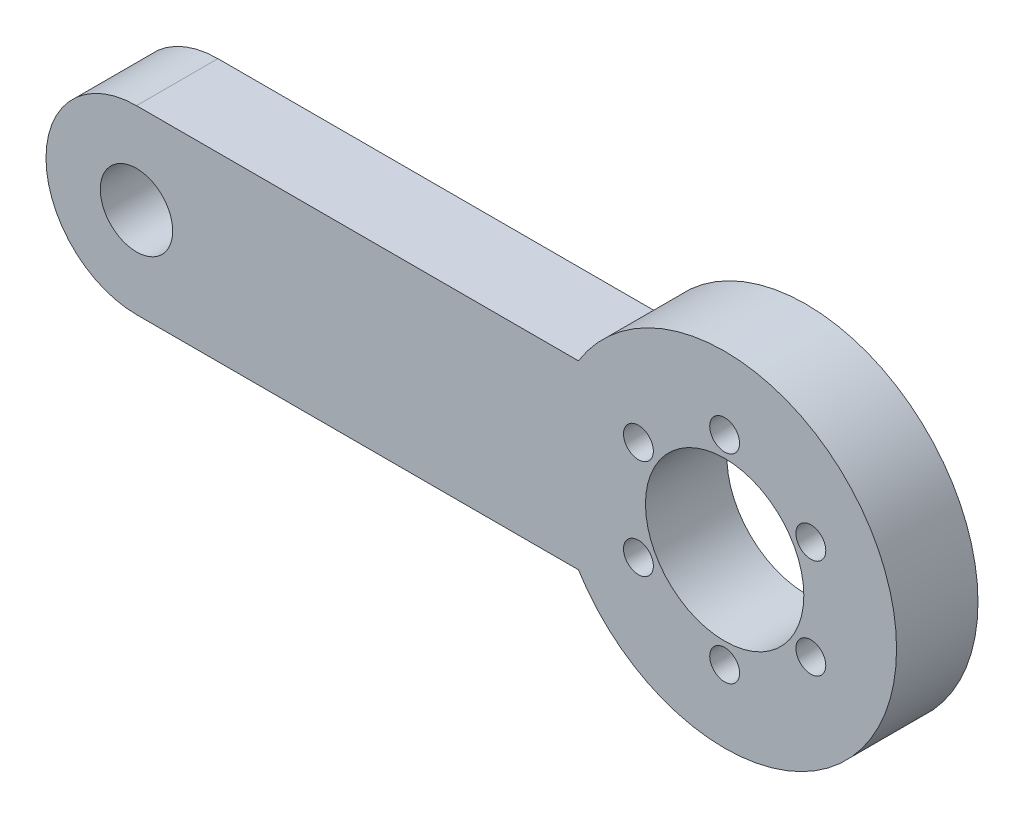
SolidWorks part; units mm, degrees
ref_plane "Plan de face" through (0, 0, 0) normal (0, 0, 1) x (1, 0, 0)
ref_plane "Plan de dessus" through (0, 0, 0) normal (0, 1, 0) x (1, 0, 0)
ref_plane "Plan de droite" through (0, 0, 0) normal (1, 0, 0) x (0, 0, -1)
sketch "Esquisse1" plane through (0, 0, 0) normal (0, 0, 1) x (1, 0, 0)
  line L1 (0, 0) -> (60, 0)
  line L2 (0, 0) -> (0, 20)
  line L3 (0, 20) -> (60, 20)
  line L4 (60, 0) -> (60, 20)
  dimension "D1" = 60
  dimension "D2" = 20
extrude "Boss.-Extru.1" add sketch "Esquisse1" along normal blind 9
sketch "Esquisse2" plane through (0, 0, 9) normal (0, 0, 1) x (1, 0, 0)
  line L0 (60, 25) -> (60, -5)
  line L1 (60, 0) -> (60, 20) construction
  line L2 (60, -5) -> (90, -5)
  line L3 (90, -5) -> (90, 25)
  line L4 (90, 10) -> (60, 10) construction
  line L5 (60, 25) -> (90, 25)
  dimension "D1" = 30
  dimension "D2" = 30
extrude "Boss.-Extru.2" add sketch "Esquisse2" against normal up to vertex (9 mm away) up to point (0, 20, 0)
sketch "Esquisse3" plane through (0, 0, 9) normal (0, 0, 1) x (1, 0, 0)
  line L0 (75, -5) -> (75, 25) construction
  line L1 (60, -5) -> (90, -5) construction
  line L2 (90, 25) -> (60, 25) construction
  circle A0 centre (75, 10) radius 8.75
  circle A1 centre (75, -1) radius 1.65
  circle A2 centre (65.4737, 4.5) radius 1.65
  circle A3 centre (65.4737, 15.5) radius 1.65
  circle A4 centre (75, 21) radius 1.65
  circle A5 centre (84.5263, 15.5) radius 1.65
  circle A6 centre (84.5263, 4.5) radius 1.65
  point P22 (75, 10)
  dimension "D1" = 17.5
  dimension "D2" = 11
  dimension "D3" = 3.3
  dimension "D4" = 6
extrude "Enlèv. mat.-Extru.1" cut sketch "Esquisse3" against normal through all both and the other way through all
sketch "Esquisse4" plane through (0, 0, 9) normal (0, 0, 1) x (1, 0, 0)
  line L0 (10, 20) -> (10, 0) construction
  line L1 (60, 20) -> (0, 20) construction
  line L2 (0, 0) -> (60, 0) construction
  line L3 (0, 20) -> (0, 0) construction
  circle A0 centre (10, 10) radius 4
  dimension "D1" = 8
  dimension "D2" = 10
extrude "Enlèv. mat.-Extru.2" cut sketch "Esquisse4" against normal through all both and the other way through all
fillet "Congé1" radius 10 2 edges at (0, 0, 4.5) (0, 20, 4.5)
sketch "Esquisse6" plane through (0, 0, 9) normal (0, 0, 1) x (1, 0, 0)
  circle A0 centre (75, 10) radius 14
  circle A1 centre (75, 10) radius 19
  dimension "D1" = 38
  dimension "D2" = 28
extrude "Boss.-Extru.3" add sketch "Esquisse6" against normal up to vertex (9 mm away) up to point (60, 25, 0)
sketch "Esquisse7" plane through (0, 0, 9) normal (0, 0, 1) x (1, 0, 0)
  line L0 (10, 0) -> (58.8445, 0) construction
  line L1 (58.8445, 0) -> (58.8445, -10.5)
  line L2 (58.8445, -10.5) -> (94.8445, -10.5)
  line L3 (94.8445, -10.5) -> (94.8445, 30.5)
  line L4 (94.8445, 10) -> (75, 10) construction
  line L5 (58.8445, 30.5) -> (94.8445, 30.5)
  line L6 (58.8445, 20) -> (58.8445, 30.5)
  circle A0 centre (75, 10) radius 19 construction
  arc A1 (58.8445, 20) -> (58.8445, 0) centre (75, 10) cw
  dimension "D1" = 38
  dimension "D2" = 36
  dimension "D3" = 41
extrude "Enlèv. mat.-Extru.4" cut sketch "Esquisse7" against normal through all
